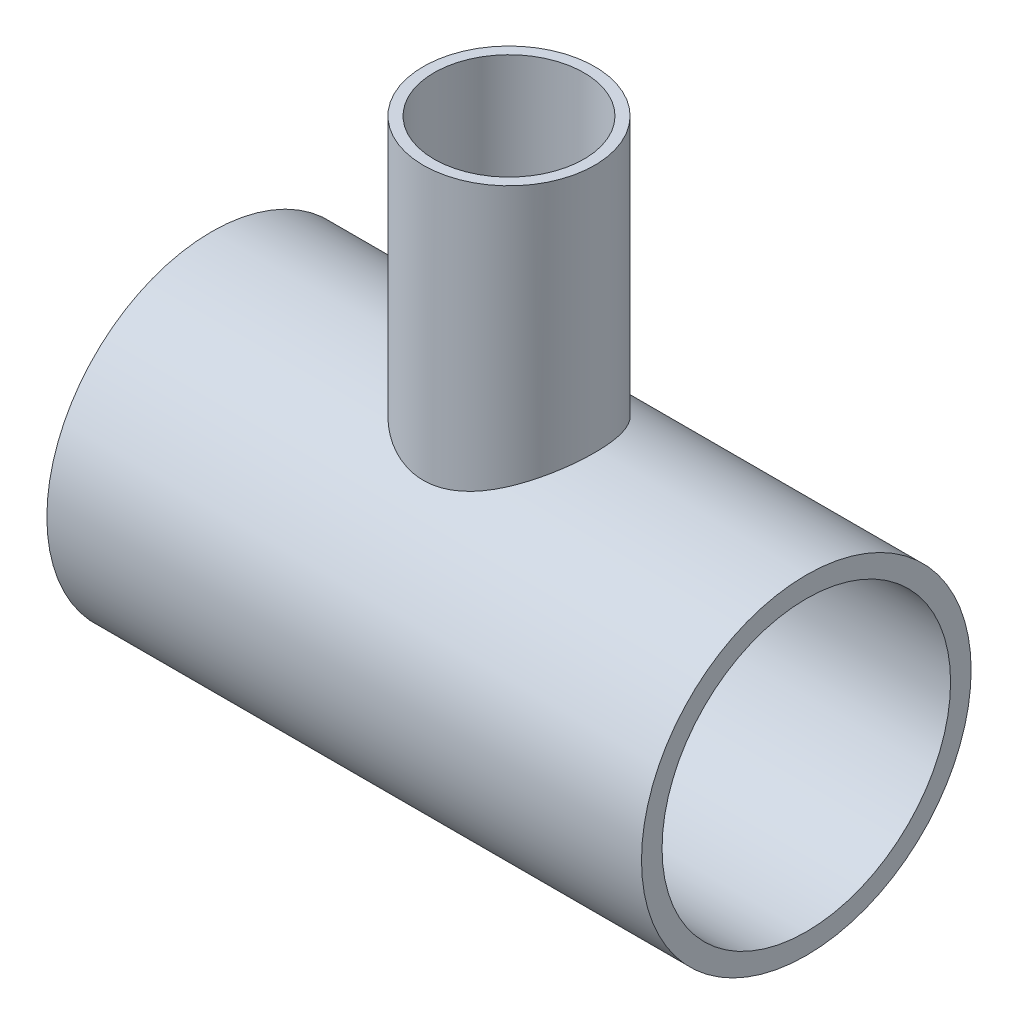
SolidWorks part; units mm, degrees
material "PE High Density"
ref_plane "Front Plane" through (0, 0, 0) normal (0, 0, 1) x (1, 0, 0)
ref_plane "Top Plane" through (0, 0, 0) normal (0, 1, 0) x (1, 0, 0)
ref_plane "Right Plane" through (0, 0, 0) normal (1, 0, 0) x (0, 0, -1)
sketch "Revolve of 12 NOM" plane through (0, 0, 0) normal (0, 0, 1) x (1, 0, 0)
  line L0 (0, 0) -> (319.0916, 0) construction
  line L1 (-292.1, 161.925) -> (292.1, 161.925)
  line L2 (-292.1, 161.925) -> (-292.1, 141.732)
  line L3 (-292.1, 141.732) -> (292.1, 141.732)
  line L4 (292.1, 161.925) -> (292.1, 141.732)
  point P7 (0, 141.732)
  point P8 (0, 0)
  dimension "D1" = 141.732
  dimension "D2" = 161.925
  dimension "D3" = 584.2
revolve "Revolve12 NOM" add sketch "Revolve of 12 NOM" angle 360 about L0
ref_plane "Offset B Plane" through (0, 406.4, 0) normal (0, 1, 0) x (1, 0, 0)
sketch "Sketch2" plane through (0, 406.4, 0) normal (0, 1, 0) x (1, 0, 0)
  line L0 (-55, 0) -> (55, 0) construction
  line L1 (292.1, -161.925) -> (292.1, 161.925) construction
  circle A0 centre (0, 0) radius 84.1375
  dimension "D2" = 168.275
  dimension "D1" = 292.1
extrude "6 NOM OD Extrude" add sketch "Sketch2" against normal up to surface (268.0505 mm away) up to face at (-292.1, 0, 161.925)
sketch "6 NOM ID Extrude" plane through (0, 406.4, 0) normal (0, 1, 0) x (1, 0, 0)
  circle A0 centre (0, 0) radius 73.6473
  dimension "D1" = 147.2946
extrude "6 NOM ID Extrude Cut" cut sketch "6 NOM ID Extrude" against normal up to surface (406.4 mm away) up to plane "Top Plane"
ref_axis "Nozzle" through (0, 115.9252, 0) along (0, 1, 0)
ref_plane "Midplane" through (0, 0, 0) normal (1, 0, 0) x (0, 0, -1)
sketch "Sketch3" plane through (0, 406.4, 0) normal (0, 1, 0) x (1, 0, 0)
  point P0 (0, 0)
equation "\"A\"= 8in'EPG Datasheet"
equation "\"B\"= 16in'EPG Datasheet"
equation "\"L\"= 23in'EPG Datasheet"
equation "\"ID 12\"= 11.16in'EPG Datasheet"
equation "\"OD 12\"= 12.75in'EPG Datasheet"
equation "\"ID 6\"= 5.799in'EPG Datasheet"
equation "\"OD 6\"= 6.625in'EPG Datasheet"
equation "\"D1@Revolve of 12 NOM\" = \"ID 12\" / 2"
equation "\"D2@Revolve of 12 NOM\" = \"OD 12\" / 2"
equation "\"D3@Revolve of 12 NOM\" = \"L\""
equation "\"D1@Sketch2\"=\"L\"/2"
equation "\"D2@Sketch2\"=\"OD 6\""
equation "\"D1@6 NOM ID Extrude\" = \"ID 6\""
